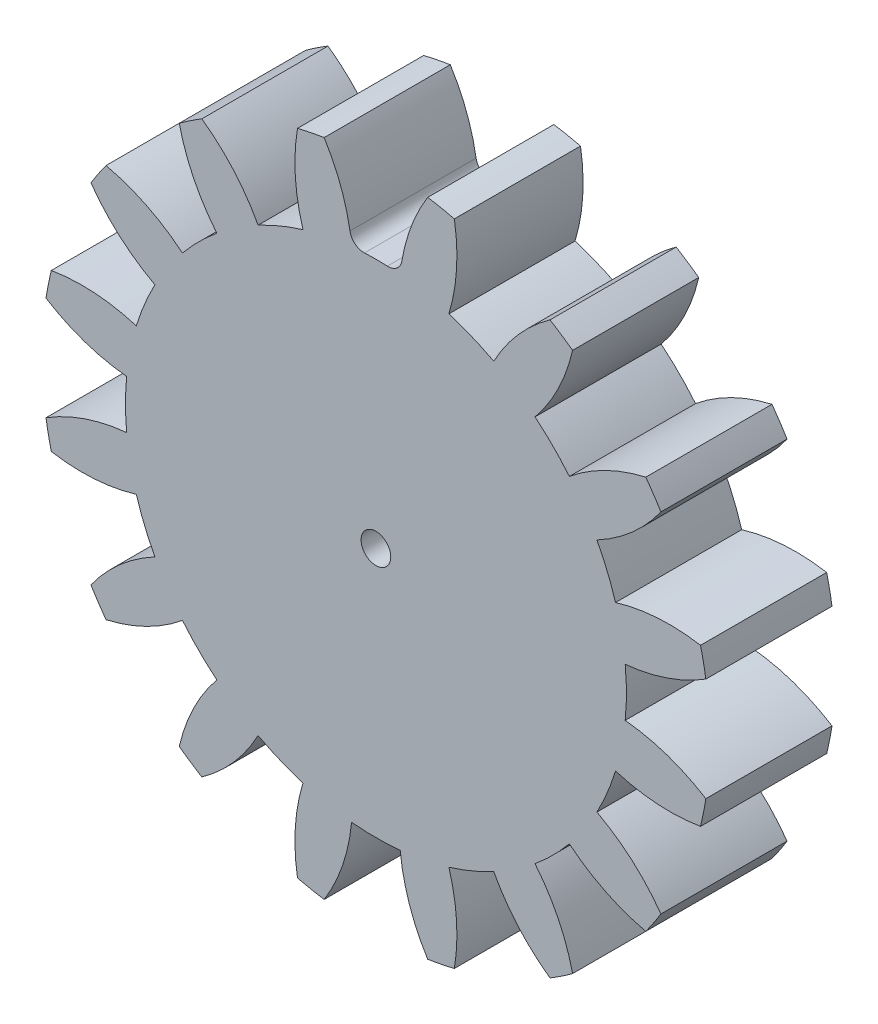
SolidWorks part; units mm, degrees
ref_plane "Front Plane" through (0, 0, 0) normal (0, 0, 1) x (1, 0, 0)
ref_plane "Top Plane" through (0, 0, 0) normal (0, 1, 0) x (1, 0, 0)
ref_plane "Right Plane" through (0, 0, 0) normal (1, 0, 0) x (0, 0, -1)
sketch "Sketch1" plane through (0, 0, 0) normal (0, 0, 1) x (1, 0, 0)
  circle A0 centre (0, 0) radius 22.5
  circle A1 centre (0, 0) radius 1
  dimension "D1" = 2
  dimension "D2" = 45
extrude "Boss-Extrude1" add sketch "Sketch1" along normal mid plane 8.5
sketch "Sketch2" plane through (0, 0, 0) normal (0, 0, 1) x (1, 0, 0)
  line L0 (0, 0) -> (0, 22.5) construction
  line L1 (0, 0) -> (-1.6371, 16.7954) construction
  line L2 (0, 13.4531) -> (-2.7041, 20.8825) construction
  arc A0 (2.3332, 19.8634) -> (-2.3332, 19.8634) centre (0, 0) ccw construction
  arc A1 (1.6371, 16.7954) -> (-1.6371, 16.7954) centre (0, 0) ccw
  circle A2 centre (0, 0) radius 22.5 construction
  arc A3 (3.488, 22.228) -> (-3.488, 22.228) centre (0, 0) ccw
  arc A4 (-1.6371, 16.7954) -> (-3.488, 22.228) centre (-14.1001, 15.5806) ccw
  arc A5 (1.6371, 16.7954) -> (3.488, 22.228) centre (14.1001, 15.5806) cw
  dimension "D1" = 40
  dimension "D2" = 5.625
  dimension "D3" = 20
  dimension "D4" = 4.677
extrude "Cut-Extrude1" cut sketch "Sketch2" against normal through all both and the other way through all
fillet "Fillet1" radius 0.95 2 edges at (1.6371, 16.7954, 0) (-1.6371, 16.7954, 0)
pattern_circular "CirPattern3" count 16 over 360 about axis through (0, 0, 4.25) along (0, 0, -1) of "Cut-Extrude1"
equation "\"Module\"= 2.5"
equation "\"Pressure Angle\"= 20"
equation "\"Bore\"= 2"
equation "\"NumTeeth\"= 16"
equation "\"D1@Sketch1\"=\"Bore\""
equation "\"D2@Sketch1\"=(\"NumTeeth\"+2)*\"Module\""
equation "\"D1@Sketch2\"=\"NumTeeth\"*\"Module\""
equation "\"ToothDepth\"= IIF ( \"Module\" < 1.25 , 2.4 * \"Module\" , 2.25 * \"Module\" )"
equation "\"D2@Sketch2\"=\"ToothDepth\""
equation "\"D3@Sketch2\"=\"Pressure Angle\""
equation "\"D4@Sketch2\"=((\"Module\"*PI)/2)+0.3*\"Module\""
equation "\"D1@Fillet1\"=\"Module\"*0.38"
equation "\"D1@CirPattern3\"=\"NumTeeth\""
